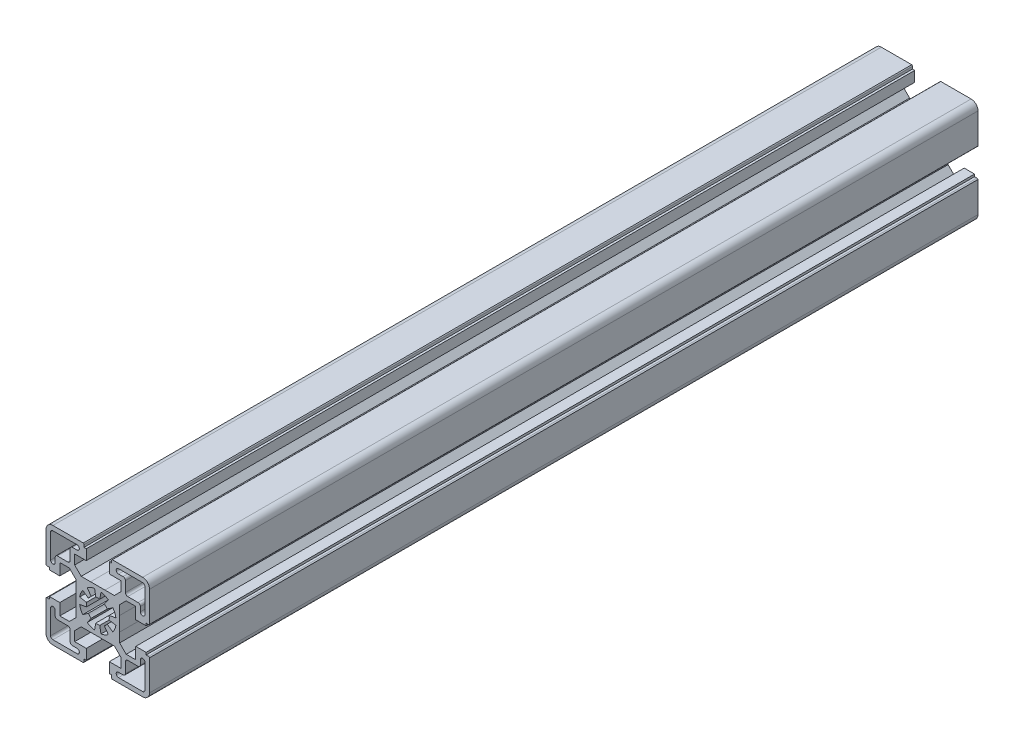
SolidWorks part; units mm, degrees
ref_plane "Front Plane" through (0, 0, 0) normal (0, 0, 1) x (1, 0, 0)
ref_plane "Top Plane" through (0, 0, 0) normal (0, 1, 0) x (1, 0, 0)
ref_plane "Right Plane" through (0, 0, 0) normal (1, 0, 0) x (0, 0, -1)
sketch "Sketch1" plane through (0, 0, 0) normal (0, 0, 1) x (1, 0, 0)
  line L0 (0, 34.901) -> (0, -38.8683) construction
  line L1 (-27.7848, -31.1091) -> (42.6814, -31.1091) construction
  line L3 (-0.8682, 4.924) -> (-1.3892, 7.8785)
  line L4 (-4.5886, 6.5532) -> (-2.8679, 4.0957)
  line L5 (-4.0957, 2.8679) -> (-6.5532, 4.5886)
  line L6 (-7.8784, 1.3892) -> (-4.924, 0.8682)
  line L10 (4.924, 0.8682) -> (7.8785, 1.3892)
  line L12 (6.5532, 4.5886) -> (4.0957, 2.8679)
  line L30 (-9.5, 3.1227) -> (-9.5, 7.207)
  line L31 (-9.5, 7.207) -> (-12.3429, 10.0499)
  line L32 (-12.3429, 10.0499) -> (-16.5, 10.0499)
  line L33 (-16.5, 10.0499) -> (-16.5, 4.9999)
  line L34 (-16.5, 4.9999) -> (-20.9999, 4.9999)
  line L35 (-20.9999, 4.9999) -> (-20.9999, 6)
  line L36 (-20.9999, 6) -> (-21.9999, 6)
  line L37 (-22.4999, 6.2999) -> (-22.4999, 19.5)
  line L38 (-19.4999, 22.5) -> (-6.3, 22.5)
  line L39 (-6, 21.9999) -> (-6, 20.9999)
  line L40 (-6, 20.9999) -> (-5, 20.9999)
  line L41 (-5, 20.9999) -> (-5, 16.5)
  line L42 (-5, 16.5) -> (-10.0501, 16.5)
  line L43 (-10.0501, 16.5) -> (-10.0501, 12.3428)
  line L44 (-10.0501, 12.3428) -> (-7.2071, 9.4999)
  line L45 (-7.2071, 9.4999) -> (-3.1228, 9.4999)
  line L82 (2.8679, 4.0957) -> (4.5886, 6.5532)
  line L83 (1.3892, 7.8784) -> (0.8682, 4.924)
  line L85 (3.1227, 9.5) -> (7.207, 9.5)
  line L86 (7.207, 9.5) -> (10.0499, 12.3429)
  line L87 (10.0499, 12.3429) -> (10.0499, 16.5)
  line L94 (-17.5001, 12) -> (-13.0001, 12)
  line L95 (-12.0001, 13) -> (-12.0001, 17.4999)
  line L96 (-11.0001, 18.4999) -> (-9.0001, 18.4999)
  line L97 (-19.5001, 20.5) -> (-9.0001, 20.5)
  line L98 (-20.5001, 8.9999) -> (-20.5001, 19.5)
  line L99 (-18.5001, 8.9999) -> (-18.5001, 11)
  line L101 (10.0499, 16.5) -> (4.9999, 16.5)
  line L102 (4.9999, 16.5) -> (4.9999, 20.9999)
  line L103 (4.9999, 20.9999) -> (6, 20.9999)
  line L104 (6, 20.9999) -> (6, 21.9999)
  line L105 (6.2999, 22.4999) -> (19.5, 22.4999)
  line L110 (22.5, 19.4999) -> (22.5, 6.3)
  line L111 (21.9999, 6) -> (20.9999, 6)
  line L118 (-3.1228, 9.4999) -> (3.1227, 9.5)
  line L119 (20.9999, 6) -> (20.9999, 5)
  line L124 (20.9999, 5) -> (16.5, 5)
  line L125 (16.5, 5) -> (16.5, 10.0501)
  line L126 (16.5, 10.0501) -> (12.3428, 10.0501)
  line L127 (12.3428, 10.0501) -> (9.4999, 7.2071)
  line L128 (9.4999, 7.2071) -> (9.4999, 3.1228)
  line L129 (12, 17.5001) -> (12, 13.0001)
  line L130 (13, 12.0001) -> (17.4999, 12.0001)
  line L131 (18.4999, 11.0001) -> (18.4999, 9.0001)
  line L132 (20.5, 19.5001) -> (20.5, 9.0001)
  line L133 (8.9999, 20.5001) -> (19.5, 20.5001)
  line L134 (8.9999, 18.5001) -> (11, 18.5001)
  line L135 (-9.5, 3.1227) -> (-9.4999, -3.1228)
  line L136 (9.4999, 3.1228) -> (9.5, -3.1227)
  line L137 (3.1228, -9.4999) -> (-3.1227, -9.5)
  line L138 (-0.8682, 4.924) -> (-1.3892, 7.8785)
  line L147 (0.8682, -4.924) -> (1.3892, -7.8785)
  line L148 (4.5886, -6.5532) -> (2.8679, -4.0957)
  line L149 (-4.924, -0.8682) -> (-7.8785, -1.3892)
  line L154 (4.0957, -2.8679) -> (6.5532, -4.5886)
  line L155 (7.8784, -1.3892) -> (4.924, -0.8682)
  line L157 (9.5, -3.1227) -> (9.5, -7.207)
  line L158 (9.5, -7.207) -> (12.3429, -10.0499)
  line L159 (12.3429, -10.0499) -> (16.5, -10.0499)
  line L160 (16.5, -10.0499) -> (16.5, -4.9999)
  line L161 (16.5, -4.9999) -> (20.9999, -4.9999)
  line L162 (20.9999, -4.9999) -> (20.9999, -6)
  line L163 (20.9999, -6) -> (21.9999, -6)
  line L164 (22.4999, -6.2999) -> (22.4999, -19.5)
  line L165 (19.4999, -22.5) -> (6.3, -22.5)
  line L166 (6, -21.9999) -> (6, -20.9999)
  line L167 (6, -20.9999) -> (5, -20.9999)
  line L168 (5, -20.9999) -> (5, -16.5)
  line L169 (5, -16.5) -> (10.0501, -16.5)
  line L176 (10.0501, -16.5) -> (10.0501, -12.3428)
  line L178 (4.924, 0.8682) -> (7.8785, 1.3892) [skipped]
  line L179 (6.5532, 4.5886) -> (4.0957, 2.8679) [skipped]
  line L180 (2.8679, 4.0957) -> (4.5886, 6.5532) [skipped]
  line L181 (1.3892, 7.8784) -> (0.8682, 4.924) [skipped]
  line L183 (3.1227, 9.5) -> (7.207, 9.5) [skipped]
  line L184 (7.207, 9.5) -> (10.0499, 12.3429) [skipped]
  line L185 (10.0499, 12.3429) -> (10.0499, 16.5) [skipped]
  line L186 (10.0499, 16.5) -> (4.9999, 16.5) [skipped]
  line L187 (4.9999, 16.5) -> (4.9999, 20.9999) [skipped]
  line L188 (4.9999, 20.9999) -> (6, 20.9999) [skipped]
  line L189 (6, 20.9999) -> (6, 21.9999) [skipped]
  line L190 (6.2999, 22.4999) -> (19.5, 22.4999) [skipped]
  line L191 (22.5, 19.4999) -> (22.5, 6.3) [skipped]
  line L192 (21.9999, 6) -> (20.9999, 6) [skipped]
  line L193 (20.9999, 6) -> (20.9999, 5) [skipped]
  line L194 (20.9999, 5) -> (16.5, 5) [skipped]
  line L195 (16.5, 5) -> (16.5, 10.0501) [skipped]
  line L196 (16.5, 10.0501) -> (12.3428, 10.0501) [skipped]
  line L197 (12.3428, 10.0501) -> (9.4999, 7.2071) [skipped]
  line L198 (9.4999, 7.2071) -> (9.4999, 3.1228) [skipped]
  line L199 (12, 17.5001) -> (12, 13.0001) [skipped]
  line L200 (13, 12.0001) -> (17.4999, 12.0001) [skipped]
  line L201 (18.4999, 11.0001) -> (18.4999, 9.0001) [skipped]
  line L202 (20.5, 19.5001) -> (20.5, 9.0001) [skipped]
  line L203 (8.9999, 20.5001) -> (19.5, 20.5001) [skipped]
  line L204 (8.9999, 18.5001) -> (11, 18.5001) [skipped]
  line L206 (0.8682, -4.924) -> (1.3892, -7.8785) [skipped]
  line L207 (4.5886, -6.5532) -> (2.8679, -4.0957) [skipped]
  line L208 (4.0957, -2.8679) -> (6.5532, -4.5886) [skipped]
  line L209 (7.8784, -1.3892) -> (4.924, -0.8682) [skipped]
  line L210 (9.5, -3.1227) -> (9.5, -7.207) [skipped]
  line L211 (9.5, -7.207) -> (12.3429, -10.0499) [skipped]
  line L212 (12.3429, -10.0499) -> (16.5, -10.0499) [skipped]
  line L213 (16.5, -10.0499) -> (16.5, -4.9999) [skipped]
  line L214 (16.5, -4.9999) -> (20.9999, -4.9999) [skipped]
  line L215 (20.9999, -4.9999) -> (20.9999, -6) [skipped]
  line L216 (20.9999, -6) -> (21.9999, -6) [skipped]
  line L217 (22.4999, -6.2999) -> (22.4999, -19.5) [skipped]
  line L218 (19.4999, -22.5) -> (6.3, -22.5) [skipped]
  line L219 (6, -21.9999) -> (6, -20.9999) [skipped]
  line L220 (6, -20.9999) -> (5, -20.9999) [skipped]
  line L221 (5, -20.9999) -> (5, -16.5) [skipped]
  line L222 (5, -16.5) -> (10.0501, -16.5) [skipped]
  line L223 (10.0501, -16.5) -> (10.0501, -12.3428) [skipped]
  line L224 (10.0501, -12.3428) -> (7.2071, -9.4999) [skipped]
  line L225 (7.2071, -9.4999) -> (3.1228, -9.4999) [skipped]
  line L226 (17.5001, -12) -> (13.0001, -12) [skipped]
  line L227 (12.0001, -13) -> (12.0001, -17.4999) [skipped]
  line L228 (11.0001, -18.4999) -> (9.0001, -18.4999) [skipped]
  line L229 (19.5001, -20.5) -> (9.0001, -20.5) [skipped]
  line L230 (20.5001, -8.9999) -> (20.5001, -19.5) [skipped]
  line L231 (18.5001, -8.9999) -> (18.5001, -11) [skipped]
  line L235 (-6.5532, -4.5886) -> (-4.0957, -2.8679) [skipped]
  line L236 (-2.8679, -4.0957) -> (-4.5886, -6.5532) [skipped]
  line L237 (-1.3892, -7.8784) -> (-0.8682, -4.924) [skipped]
  line L238 (-3.1227, -9.5) -> (-7.207, -9.5) [skipped]
  line L239 (-7.207, -9.5) -> (-10.0499, -12.3429) [skipped]
  line L240 (-10.0499, -12.3429) -> (-10.0499, -16.5) [skipped]
  line L241 (-10.0499, -16.5) -> (-4.9999, -16.5) [skipped]
  line L242 (-4.9999, -16.5) -> (-4.9999, -20.9999) [skipped]
  line L243 (-4.9999, -20.9999) -> (-6, -20.9999) [skipped]
  line L244 (-6, -20.9999) -> (-6, -21.9999) [skipped]
  line L245 (-6.2999, -22.4999) -> (-19.5, -22.4999) [skipped]
  line L246 (-22.5, -19.4999) -> (-22.5, -6.3) [skipped]
  line L247 (-21.9999, -6) -> (-20.9999, -6) [skipped]
  line L248 (-20.9999, -6) -> (-20.9999, -5) [skipped]
  line L249 (-20.9999, -5) -> (-16.5, -5) [skipped]
  line L250 (-16.5, -5) -> (-16.5, -10.0501) [skipped]
  line L251 (-16.5, -10.0501) -> (-12.3428, -10.0501) [skipped]
  line L252 (-12.3428, -10.0501) -> (-9.4999, -7.2071) [skipped]
  line L253 (-9.4999, -7.2071) -> (-9.4999, -3.1228) [skipped]
  line L254 (-12, -17.5001) -> (-12, -13.0001) [skipped]
  line L255 (-13, -12.0001) -> (-17.4999, -12.0001) [skipped]
  line L256 (-18.4999, -11.0001) -> (-18.4999, -9.0001) [skipped]
  line L257 (-20.5, -19.5001) -> (-20.5, -9.0001) [skipped]
  line L258 (-8.9999, -20.5001) -> (-19.5, -20.5001) [skipped]
  line L259 (-8.9999, -18.5001) -> (-11, -18.5001) [skipped]
  line L261 (10.0501, -12.3428) -> (7.2071, -9.4999)
  line L262 (7.2071, -9.4999) -> (3.1228, -9.4999)
  line L263 (17.5001, -12) -> (13.0001, -12)
  line L264 (12.0001, -13) -> (12.0001, -17.4999)
  line L265 (11.0001, -18.4999) -> (9.0001, -18.4999)
  line L266 (19.5001, -20.5) -> (9.0001, -20.5)
  line L267 (20.5001, -8.9999) -> (20.5001, -19.5)
  line L268 (18.5001, -8.9999) -> (18.5001, -11)
  line L272 (4.924, 0.8682) -> (7.8785, 1.3892)
  line L275 (-4.924, -0.8682) -> (-7.8785, -1.3892)
  line L276 (-6.5532, -4.5886) -> (-4.0957, -2.8679)
  line L277 (-2.8679, -4.0957) -> (-4.5886, -6.5532)
  line L278 (-1.3892, -7.8784) -> (-0.8682, -4.924)
  line L280 (-3.1227, -9.5) -> (-7.207, -9.5)
  line L281 (-7.207, -9.5) -> (-10.0499, -12.3429)
  line L282 (-10.0499, -12.3429) -> (-10.0499, -16.5)
  line L283 (-10.0499, -16.5) -> (-4.9999, -16.5)
  line L284 (-4.9999, -16.5) -> (-4.9999, -20.9999)
  line L285 (-4.9999, -20.9999) -> (-6, -20.9999)
  line L286 (-6, -20.9999) -> (-6, -21.9999)
  line L287 (-6.2999, -22.4999) -> (-19.5, -22.4999)
  line L288 (-22.5, -19.4999) -> (-22.5, -6.3)
  line L289 (-21.9999, -6) -> (-20.9999, -6)
  line L290 (-20.9999, -6) -> (-20.9999, -5)
  line L291 (-20.9999, -5) -> (-16.5, -5)
  line L292 (-16.5, -5) -> (-16.5, -10.0501)
  line L293 (-16.5, -10.0501) -> (-12.3428, -10.0501)
  line L294 (-12.3428, -10.0501) -> (-9.4999, -7.2071)
  line L295 (-9.4999, -7.2071) -> (-9.4999, -3.1228)
  line L296 (-12, -17.5001) -> (-12, -13.0001)
  line L297 (-13, -12.0001) -> (-17.4999, -12.0001)
  line L298 (-18.4999, -11.0001) -> (-18.4999, -9.0001)
  line L299 (-20.5, -19.5001) -> (-20.5, -9.0001)
  line L300 (-8.9999, -20.5001) -> (-19.5, -20.5001)
  line L301 (-8.9999, -18.5001) -> (-11, -18.5001)
  line L305 (0.8682, -4.924) -> (1.3892, -7.8785)
  arc A1 (-1.3892, 7.8785) -> (-4.5886, 6.5532) centre (0, 0) ccw
  arc A2 (-2.8679, 4.0957) -> (-4.0957, 2.8679) centre (0, 0) ccw
  arc A3 (-6.5532, 4.5886) -> (-7.8784, 1.3892) centre (0, 0) ccw
  arc A4 (-4.924, 0.8682) -> (-4.924, -0.8682) centre (0, 0) ccw
  arc A7 (0.8682, 4.924) -> (-0.8682, 4.924) centre (0, 0) ccw
  arc A8 (7.8785, 1.3892) -> (6.5532, 4.5886) centre (0, 0) ccw
  arc A20 (-22.4999, 6.2999) -> (-21.9999, 6) centre (-22.041, 6.4983) ccw
  arc A21 (-19.4999, 22.5) -> (-22.4999, 19.5) centre (-19.4999, 19.5) ccw
  arc A22 (-6, 21.9999) -> (-6.3, 22.5) centre (-6.4984, 22.041) ccw
  arc A32 (4.0957, 2.8679) -> (2.8679, 4.0957) centre (0, 0) ccw
  arc A33 (4.5886, 6.5532) -> (1.3892, 7.8784) centre (0, 0) ccw
  arc A44 (-17.5001, 12) -> (-18.5001, 11) centre (-17.5001, 11) ccw
  arc A45 (-13.0001, 12) -> (-12.0001, 13) centre (-13.0001, 13) ccw
  arc A46 (-11.0001, 18.4999) -> (-12.0001, 17.4999) centre (-11.0001, 17.4999) ccw
  arc A47 (-9.0001, 18.4999) -> (-9.0001, 20.5) centre (-9.0001, 19.5) ccw
  arc A48 (-19.5001, 20.5) -> (-20.5001, 19.5) centre (-19.5001, 19.5) ccw
  arc A49 (-20.5001, 8.9999) -> (-18.5001, 8.9999) centre (-19.5001, 8.9999) ccw
  arc A51 (0.8682, 4.924) -> (-0.8682, 4.924) centre (0, 0) ccw
  arc A52 (4.924, -0.8682) -> (4.924, 0.8682) centre (0, 0) ccw
  arc A53 (6.2999, 22.4999) -> (6, 21.9999) centre (6.4983, 22.041) ccw
  arc A60 (-7.8785, -1.3892) -> (-6.5532, -4.5886) centre (0, 0) ccw
  arc A64 (22.5, 19.4999) -> (19.5, 22.4999) centre (19.5, 19.4999) ccw
  arc A65 (21.9999, 6) -> (22.5, 6.3) centre (22.041, 6.4984) ccw
  arc A66 (12, 17.5001) -> (11, 18.5001) centre (11, 17.5001) ccw
  arc A73 (7.8785, 1.3892) -> (6.5532, 4.5886) centre (0, 0) ccw [skipped]
  arc A74 (4.0957, 2.8679) -> (2.8679, 4.0957) centre (0, 0) ccw [skipped]
  arc A75 (4.5886, 6.5532) -> (1.3892, 7.8784) centre (0, 0) ccw [skipped]
  arc A76 (6.2999, 22.4999) -> (6, 21.9999) centre (6.4983, 22.041) ccw [skipped]
  arc A77 (22.5, 19.4999) -> (19.5, 22.4999) centre (19.5, 19.4999) ccw [skipped]
  arc A78 (21.9999, 6) -> (22.5, 6.3) centre (22.041, 6.4984) ccw [skipped]
  arc A79 (12, 17.5001) -> (11, 18.5001) centre (11, 17.5001) ccw [skipped]
  arc A80 (12, 13.0001) -> (13, 12.0001) centre (13, 13.0001) ccw [skipped]
  arc A81 (18.4999, 11.0001) -> (17.4999, 12.0001) centre (17.4999, 11.0001) ccw [skipped]
  arc A82 (18.4999, 9.0001) -> (20.5, 9.0001) centre (19.5, 9.0001) ccw [skipped]
  arc A83 (20.5, 19.5001) -> (19.5, 20.5001) centre (19.5, 19.5001) ccw [skipped]
  arc A84 (8.9999, 20.5001) -> (8.9999, 18.5001) centre (8.9999, 19.5001) ccw [skipped]
  arc A85 (1.3892, -7.8785) -> (4.5886, -6.5532) centre (0, 0) ccw [skipped]
  arc A86 (2.8679, -4.0957) -> (4.0957, -2.8679) centre (0, 0) ccw [skipped]
  arc A87 (6.5532, -4.5886) -> (7.8784, -1.3892) centre (0, 0) ccw [skipped]
  arc A88 (4.924, -0.8682) -> (4.924, 0.8682) centre (0, 0) ccw [skipped]
  arc A89 (22.4999, -6.2999) -> (21.9999, -6) centre (22.041, -6.4983) ccw [skipped]
  arc A90 (19.4999, -22.5) -> (22.4999, -19.5) centre (19.4999, -19.5) ccw [skipped]
  arc A91 (6, -21.9999) -> (6.3, -22.5) centre (6.4984, -22.041) ccw [skipped]
  arc A92 (17.5001, -12) -> (18.5001, -11) centre (17.5001, -11) ccw [skipped]
  arc A93 (13.0001, -12) -> (12.0001, -13) centre (13.0001, -13) ccw [skipped]
  arc A94 (11.0001, -18.4999) -> (12.0001, -17.4999) centre (11.0001, -17.4999) ccw [skipped]
  arc A95 (9.0001, -18.4999) -> (9.0001, -20.5) centre (9.0001, -19.5) ccw [skipped]
  arc A96 (19.5001, -20.5) -> (20.5001, -19.5) centre (19.5001, -19.5) ccw [skipped]
  arc A97 (20.5001, -8.9999) -> (18.5001, -8.9999) centre (19.5001, -8.9999) ccw [skipped]
  arc A98 (-4.0957, -2.8679) -> (-2.8679, -4.0957) centre (0, 0) ccw [skipped]
  arc A99 (-4.5886, -6.5532) -> (-1.3892, -7.8784) centre (0, 0) ccw [skipped]
  arc A100 (-0.8682, -4.924) -> (0.8682, -4.924) centre (0, 0) ccw [skipped]
  arc A101 (-6.2999, -22.4999) -> (-6, -21.9999) centre (-6.4983, -22.041) ccw [skipped]
  arc A102 (-22.5, -19.4999) -> (-19.5, -22.4999) centre (-19.5, -19.4999) ccw [skipped]
  arc A103 (-21.9999, -6) -> (-22.5, -6.3) centre (-22.041, -6.4984) ccw [skipped]
  arc A104 (-12, -17.5001) -> (-11, -18.5001) centre (-11, -17.5001) ccw [skipped]
  arc A105 (-12, -13.0001) -> (-13, -12.0001) centre (-13, -13.0001) ccw [skipped]
  arc A106 (-18.4999, -11.0001) -> (-17.4999, -12.0001) centre (-17.4999, -11.0001) ccw [skipped]
  arc A107 (-18.4999, -9.0001) -> (-20.5, -9.0001) centre (-19.5, -9.0001) ccw [skipped]
  arc A108 (-20.5, -19.5001) -> (-19.5, -20.5001) centre (-19.5, -19.5001) ccw [skipped]
  arc A109 (-8.9999, -20.5001) -> (-8.9999, -18.5001) centre (-8.9999, -19.5001) ccw [skipped]
  arc A110 (12, 13.0001) -> (13, 12.0001) centre (13, 13.0001) ccw
  arc A111 (18.4999, 11.0001) -> (17.4999, 12.0001) centre (17.4999, 11.0001) ccw
  arc A112 (18.4999, 9.0001) -> (20.5, 9.0001) centre (19.5, 9.0001) ccw
  arc A113 (20.5, 19.5001) -> (19.5, 20.5001) centre (19.5, 19.5001) ccw
  arc A114 (8.9999, 20.5001) -> (8.9999, 18.5001) centre (8.9999, 19.5001) ccw
  arc A115 (-1.3892, 7.8785) -> (-4.5886, 6.5532) centre (0, 0) ccw
  arc A116 (1.3892, -7.8785) -> (4.5886, -6.5532) centre (0, 0) ccw
  arc A117 (2.8679, -4.0957) -> (4.0957, -2.8679) centre (0, 0) ccw
  arc A118 (6.5532, -4.5886) -> (7.8784, -1.3892) centre (0, 0) ccw
  arc A119 (4.924, -0.8682) -> (4.924, 0.8682) centre (0, 0) ccw
  arc A120 (-0.8682, -4.924) -> (0.8682, -4.924) centre (0, 0) ccw
  arc A121 (22.4999, -6.2999) -> (21.9999, -6) centre (22.041, -6.4983) ccw
  arc A122 (19.4999, -22.5) -> (22.4999, -19.5) centre (19.4999, -19.5) ccw
  arc A123 (6, -21.9999) -> (6.3, -22.5) centre (6.4984, -22.041) ccw
  arc A124 (17.5001, -12) -> (18.5001, -11) centre (17.5001, -11) ccw
  arc A125 (13.0001, -12) -> (12.0001, -13) centre (13.0001, -13) ccw
  arc A126 (11.0001, -18.4999) -> (12.0001, -17.4999) centre (11.0001, -17.4999) ccw
  arc A127 (9.0001, -18.4999) -> (9.0001, -20.5) centre (9.0001, -19.5) ccw
  arc A128 (19.5001, -20.5) -> (20.5001, -19.5) centre (19.5001, -19.5) ccw
  arc A129 (20.5001, -8.9999) -> (18.5001, -8.9999) centre (19.5001, -8.9999) ccw
  arc A130 (7.8785, 1.3892) -> (6.5532, 4.5886) centre (0, 0) ccw
  arc A131 (-7.8785, -1.3892) -> (-6.5532, -4.5886) centre (0, 0) ccw
  arc A132 (-4.0957, -2.8679) -> (-2.8679, -4.0957) centre (0, 0) ccw
  arc A133 (-4.5886, -6.5532) -> (-1.3892, -7.8784) centre (0, 0) ccw
  arc A134 (-0.8682, -4.924) -> (0.8682, -4.924) centre (0, 0) ccw
  arc A135 (-4.924, 0.8682) -> (-4.924, -0.8682) centre (0, 0) ccw
  arc A136 (-6.2999, -22.4999) -> (-6, -21.9999) centre (-6.4983, -22.041) ccw
  arc A137 (-22.5, -19.4999) -> (-19.5, -22.4999) centre (-19.5, -19.4999) ccw
  arc A138 (-21.9999, -6) -> (-22.5, -6.3) centre (-22.041, -6.4984) ccw
  arc A139 (-12, -17.5001) -> (-11, -18.5001) centre (-11, -17.5001) ccw
  arc A140 (-12, -13.0001) -> (-13, -12.0001) centre (-13, -13.0001) ccw
  arc A141 (-18.4999, -11.0001) -> (-17.4999, -12.0001) centre (-17.4999, -11.0001) ccw
  arc A142 (-18.4999, -9.0001) -> (-20.5, -9.0001) centre (-19.5, -9.0001) ccw
  arc A143 (-20.5, -19.5001) -> (-19.5, -20.5001) centre (-19.5, -19.5001) ccw
  arc A144 (-8.9999, -20.5001) -> (-8.9999, -18.5001) centre (-8.9999, -19.5001) ccw
  arc A145 (1.3892, -7.8785) -> (4.5886, -6.5532) centre (0, 0) ccw
  point P528 (0, 0)
  dimension "D1" = 4
  dimension "D2" = 4
extrude "Boss-Extrude1" add sketch "Sketch1" along normal blind 360 contours L277 A131 L101 L169 L45 L44 L43 L42 L41 L40 L39 A22 L38 A21 L37 A20 L36 L35 L34 L33 region at (-8.8636, 5.1649, 0)
